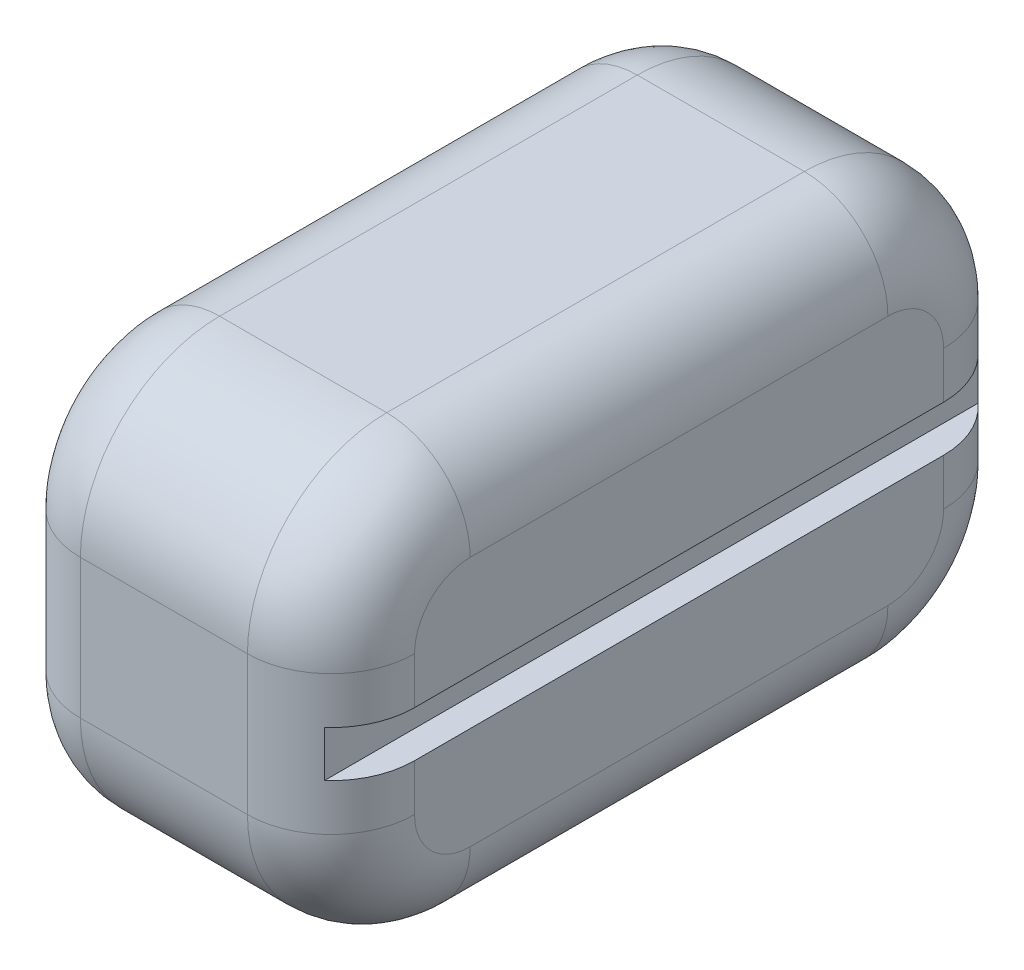
SolidWorks part; units mm, degrees
ref_plane "Front Plane" through (0, 0, 0) normal (0, 0, 1) x (1, 0, 0)
ref_plane "Top Plane" through (0, 0, 0) normal (0, 1, 0) x (1, 0, 0)
ref_plane "Right Plane" through (0, 0, 0) normal (1, 0, 0) x (0, 0, -1)
sketch "Sketch1" plane through (0, 0, 0) normal (1, 0, 0) x (0, 0, -1)
  line L1 (-12.5, -7.5) -> (12.5, -7.5)
  line L2 (-12.5, -7.5) -> (-12.5, 7.5)
  line L3 (-12.5, 7.5) -> (12.5, 7.5)
  line L4 (12.5, -7.5) -> (12.5, 7.5)
  line L5 (0, 7.5) -> (0, -7.5) construction
  line L6 (-12.5, 0) -> (12.5, 0) construction
  point P0 (0, 0)
  dimension "D1" = 15
  dimension "D2" = 25
extrude "Boss-Extrude1" add sketch "Sketch1" along normal blind 12
sketch "Sketch2" plane through (0, 0, 0) normal (0, 1, 0) x (1, 0, 0)
  line L66 (2, 10.5) -> (10, -10.5) construction
  line L76 (0, 0) -> (2, 0) construction
  line L81 (0, -5) -> (2, -5)
  line L82 (0, 5) -> (2, 5)
  line L83 (2, 10.5) -> (2, -10.5)
  line L84 (10, 10.5) -> (2, 10.5)
  line L85 (10, -10.5) -> (10, 10.5)
  line L86 (2, -10.5) -> (10, -10.5)
  line L87 (2, 9.798) -> (2, 5)
  line L88 (10, 10.5) -> (2, 10.5) construction
  line L89 (10, -10.5) -> (10, 10.5) construction
  line L90 (2, -10.5) -> (10, -10.5) construction
  line L91 (0, 5) -> (0, -5)
  line L92 (2, -5) -> (2, -9.798)
  arc A12 (2, -9.798) -> (2, 9.798) centre (0, 0) ccw
  point P4 (0, -3)
  point P5 (10, -3)
  point P7 (0, 3)
  point P9 (10, 3)
  dimension "D3" = 5
  dimension "D2" = 5
  dimension "D1" = 2
extrude "Cut-Extrude1" cut sketch "Sketch2" against normal mid plane 8
ref_plane "Plane1" through (0, -3.8, 0) normal (0, 1, 0) x (1, 0, 0)
sketch "Sketch3" plane through (0, -3.8, 0) normal (0, 1, 0) x (1, 0, 0)
  line L64 (0, -4) -> (2, -4)
  line L65 (0, -4) -> (2.25, -4)
  line L66 (0, 4) -> (0, -4)
  line L67 (0.25, 4.75) -> (0.25, -4.75)
  line L68 (0.25, -4.75) -> (2.25, -4.75)
  line L69 (2.25, -4.75) -> (2.25, -9.4868)
  line L70 (2.25, 9.4868) -> (2.25, 4.75)
  line L71 (2.25, 4.75) -> (0.25, 4.75)
  line L74 (2.25, -4.75) -> (2.25, -9.4868)
  line L75 (2.25, 9.4868) -> (2.25, 4)
  line L77 (2, 4) -> (0, 4)
  line L78 (2.25, 4) -> (0, 4)
  line L79 (2.25, -4) -> (2.25, -4.75)
  arc A15 (2.25, -9.4868) -> (2.25, 9.4868) centre (0, 0) ccw
  arc A16 (2.25, -9.4868) -> (2.25, 9.4868) centre (0, 0) ccw
  point P0 (2.7838, 2.4205)
  point P1 (0.3759, 2.0106)
  point P2 (0.3759, -2.0106)
  point P3 (2.7838, -2.4205)
  dimension "D2" = 1
  dimension "D1" = 0.25
  dimension "D3" = 1
extrude "Boss-Extrude2" add sketch "Sketch3" along normal blind 7.6 separate body
fillet "Fillet3" radius 1 2 edges at (2, 0, 5) (2, 0, -5)
fillet "Fillet6" radius 1 2 edges at (2.25, 0, -4) (2.25, 0, 4)
sketch "Sketch16" plane through (0, 0, 0) normal (-1, 0, 0) x (0, 0, 1)
  circle A0 centre (0, 0) radius 1.8
  dimension "D1" = 3.6
extrude "Cut-Extrude6" cut sketch "Sketch16" against normal blind 7
sketch "Sketch17" plane through (0, 0, 0) normal (-1, 0, 0) x (0, 0, 1)
  circle A0 centre (0, 0) radius 1.8 construction
  circle A1 centre (0, 0) radius 1.8
curve "Helix/Spiral3" pitch 5 height 5 radius 1.8 centre (0, 0, 0) axis (1, 0, 0) start towards (0, 1, 0)
sketch "Sketch18" plane through (0, 0, 0) normal (0, 0, 1) x (1, 0, 0)
  line L5 (0, 1.8) -> (0.75, 1.8)
  line L6 (0.75, 1.8) -> (0, 3.3)
  line L7 (0, 7.5) -> (0, -7.5) construction
  line L8 (0, 3.3) -> (-0.75, 1.8)
  line L9 (-0.75, 1.8) -> (0, 1.8)
  dimension "D1" = 0.75
  dimension "D2" = 1.5
sweep "Cut-Sweep3" cut profiles "Sketch18" path "Helix/Spiral3" align with end faces yes
fillet "Fillet1" radius 5 4 edges at (6, -7.5, -12.5) (6, -7.5, 12.5) (6, 7.5, 12.5) (6, 7.5, -12.5)
fillet "Fillet2" radius 3 16 edges at (0, -6.0355, -11.0355) (0, -7.5, 0) (0, -6.0355, 11.0355) (0, 0, 12.5) (0, 6.0355, 11.0355) (0, 7.5, 0) (0, 6.0355, -11.0355) (12, -6.0355, 11.0355) (12, 0, 12.5) (12, 6.0355, 11.0355) (12, 7.5, 0) (12, 6.0355, -11.0355) (12, 0, -12.5) (12, -6.0355, -11.0355) (12, -7.5, 0) (0, 0, -12.5)
sketch "Sketch8" plane through (12, 0, 0) normal (1, 0, 0) x (0, 0, -1)
  line L0 (-12.5, -2.5) -> (-12.5, 2.5) construction
  line L1 (12.5, -0.825) -> (-12.5, -0.825)
  line L2 (12.5, -0.825) -> (12.5, 0.825)
  line L3 (12.5, 0.825) -> (-12.5, 0.825)
  line L4 (-12.5, -0.825) -> (-12.5, 0.825)
  line L5 (0, 0.825) -> (0, -0.825) construction
  line L6 (12.5, 0) -> (-12.5, 0) construction
  point P0 (0, 0)
  dimension "D1" = 1.65
extrude "Cut-Extrude3" cut sketch "Sketch8" against normal blind 1
